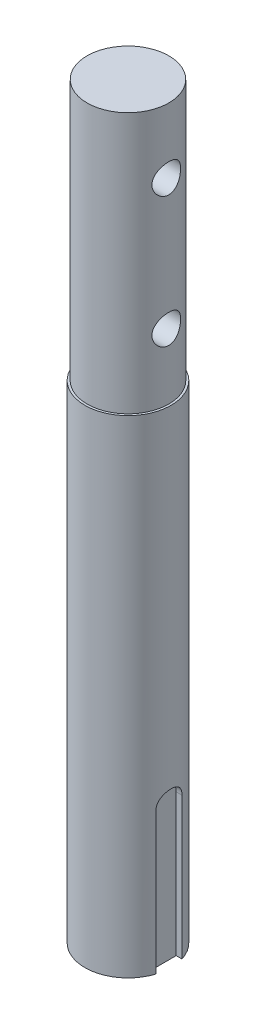
SolidWorks part; units mm, degrees
material "ASTM A36 Steel"
ref_plane "Front Plane" through (0, 0, 0) normal (0, 0, 1) x (1, 0, 0)
ref_plane "Top Plane" through (0, 0, 0) normal (0, 1, 0) x (1, 0, 0)
ref_plane "Right Plane" through (0, 0, 0) normal (1, 0, 0) x (0, 0, -1)
sketch "Sketch1" plane through (0, 0, 0) normal (0, 1, 0) x (1, 0, 0)
  circle A0 centre (0, 0) radius 33
  dimension "D1" = 66
extrude "Boss-Extrude1" add sketch "Sketch1" along normal blind 373.5
sketch "Sketch2" plane through (0, 373.5, 0) normal (0, 1, 0) x (1, 0, 0)
  circle A0 centre (0, 0) radius 31.34
  dimension "D1" = 62.68
extrude "Boss-Extrude2" add sketch "Sketch2" along normal blind 200
ref_plane "Plane1" through (33, 0, 0) normal (1, 0, 0) x (0, 0, -1)
sketch "Sketch3" plane through (33, 0, 0) normal (1, 0, 0) x (0, 0, -1)
  line L0 (-10, 108.8) -> (-10, 0)
  line L1 (-33, 0) -> (33, 0) construction
  line L2 (10, 108.8) -> (10, 0)
  line L3 (10, 0) -> (-10, 0)
  arc A0 (10, 108.8) -> (-10, 108.8) centre (0, 108.8) ccw
  dimension "D1" = 20
  dimension "D2" = 108.8
extrude "Cut-Extrude1" cut sketch "Sketch3" against normal blind 6
sketch "Sketch5" plane through (0, 0, 0) normal (1, 0, 0) x (0, 0, -1)
  line L0 (31.34, 573.5) -> (-31.34, 573.5) construction
  circle A0 centre (0, 523.5) radius 11
  circle A1 centre (0, 423.5) radius 11
  dimension "D1" = 22
  dimension "D2" = 22
  dimension "D3" = 50
  dimension "D4" = 100
extrude "Cut-Extrude2" cut sketch "Sketch5" against normal through all both and the other way through all
sketch "Sketch6" plane through (0, 0, 0) normal (0, -1, 0) x (1, 0, 0)
  circle A0 centre (0, 0) radius 5
  dimension "D1" = 10
extrude "Cut-Extrude3" cut sketch "Sketch6" against normal blind 50
thread "Thread1" pitch 1.25 method cut profile "Thread Profile1" start angle 0, offset 0, length 47, pitch 1.25, diameter 10
ref_plane "Plane2" through (5, 0, 0) normal (0, 0, 1) x (1, 0, 0)
sketch "Thread Profile1" plane through (5, 0, 0) normal (0, 0, 1) x (1, 0, 0)
  line L0 (0, 0) -> (0, 1.25) construction
  line L1 (0, 0) -> (0.6766, 0.3906)
  line L2 (0.6766, 0.3906) -> (0.6766, 0.5469)
  line L3 (0.6766, 0.5469) -> (0, 0.9375)
  line L4 (0.6766, 0.4687) -> (0, 0.4687) construction
  line L11 (0, 0) -> (0, 0.9375)
  point P2 (0, 0)
  dimension "Pitch" = 1.25
  dimension "Profile_Angle" = 60
  dimension "Profile_Land" = 0.1562
  dimension "Profile_Height" = 0.6766
